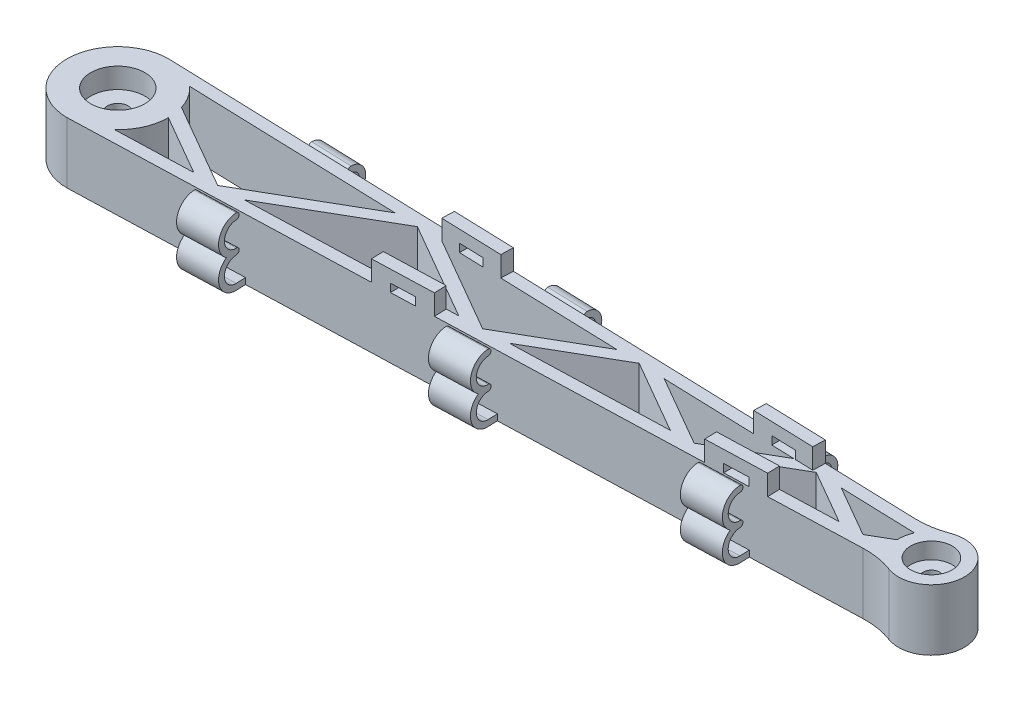
SolidWorks part; units mm, degrees
ref_plane "Front Plane" through (0, 0, 0) normal (0, 0, 1) x (1, 0, 0)
ref_plane "Top Plane" through (0, 0, 0) normal (0, 1, 0) x (1, 0, 0)
ref_plane "Right Plane" through (0, 0, 0) normal (1, 0, 0) x (0, 0, -1)
sketch "Sketch1" plane through (0, 0, 0) normal (0, 1, 0) x (1, 0, 0)
  line L0 (200, -6) -> (200, 6)
  line L1 (200, 6) -> (0, 12.5)
  line L2 (200, -6) -> (0, -12.5)
  line L3 (8.4358, 9.2243) -> (60.6202, 7.5283)
  line L4 (8.4358, -9.2243) -> (27.3057, -8.611)
  line L5 (197, 3.0959) -> (197, 2.5702)
  line L6 (32.986, -8.4264) -> (60.6202, 7.5283)
  line L7 (0, 0) -> (47.5809, 0) construction
  line L8 (39.3439, -8.2197) -> (66.3005, 7.3437)
  line L9 (32.986, -8.4264) -> (11.9305, 3.73)
  line L10 (66.3005, 7.3437) -> (90.3839, -6.5609)
  line L11 (72.6584, 7.137) -> (96.0642, -6.3763)
  line L12 (27.3057, -8.611) -> (12.4998, -0.0628)
  line L13 (96.0642, -6.3763) -> (116.9753, 5.6967)
  line L14 (102.4221, -6.1697) -> (122.6556, 5.5121)
  line L15 (122.6556, 5.5121) -> (140.7325, -4.9246)
  line L16 (129.0135, 5.3055) -> (146.4127, -4.74)
  line L17 (146.4127, -4.74) -> (161.9575, 4.2348)
  line L18 (152.7706, -4.5334) -> (167.6378, 4.0502)
  line L19 (167.6378, 4.0502) -> (180.9204, -3.6185)
  line L20 (173.9957, 3.8436) -> (186.6006, -3.4339)
  line L21 (186.6006, -3.4339) -> (197, 2.5702)
  line L22 (192.9585, -3.2273) -> (197, -0.8939)
  line L23 (197, -0.8939) -> (197, -3.0959)
  line L24 (173.9957, 3.8436) -> (197, 3.0959)
  line L25 (192.9585, -3.2273) -> (197, -3.0959)
  line L26 (180.6529, 0) -> (192.5483, 0) construction
  line L27 (160.6227, 0) -> (174.6529, 0) construction
  line L28 (152.7706, -4.5334) -> (180.9204, -3.6185)
  line L29 (129.0135, 5.3055) -> (161.9575, 4.2348)
  line L30 (138.2028, 0) -> (154.6227, 0) construction
  line L31 (113.1083, 0) -> (132.2028, 0) construction
  line L32 (102.4221, -6.1697) -> (140.7325, -4.9246)
  line L33 (85.02, 0) -> (107.1083, 0) construction
  line L34 (72.6584, 7.137) -> (116.9753, 5.6967)
  line L35 (53.5809, 0) -> (79.02, 0) construction
  line L36 (39.3439, -8.2197) -> (90.3839, -6.5609)
  circle A0 centre (0, 0) radius 6.65
  arc A1 (0, 12.5) -> (0, -12.5) centre (0, 0) ccw
  arc A2 (8.4358, -9.2243) -> (12.5, 0) centre (0, 0) ccw
  arc A3 (11.9305, 3.73) -> (8.4358, 9.2243) centre (0, 0) ccw
  point P6 (200, 0)
  dimension "D1" = 13.3
  dimension "D4" = 25
  dimension "D2" = 12
  dimension "D3" = 200
  dimension "D5" = 3
  dimension "D6" = 3
  dimension "D7" = 3
  dimension "D8" = 150
  dimension "D9" = 150
  dimension "D10" = 3
  dimension "D11" = 3
  dimension "D12" = 3
  dimension "D13" = 3
  dimension "D14" = 3
  dimension "D15" = 3
  dimension "D16" = 3
  dimension "D17" = 3
extrude "Boss-Extrude1" add sketch "Sketch1" along normal blind 15 contours L1 A1 L2 L0 L11 L34 L13 L16 L29 L17 L20 L24 L5 L21 L25 L22 L23 L28 L18 L19 L32 L14 L15 L36 L8 L10 A0 L4 A2 L12 L9 A3 L3 L6 region at (99.9305, 0, 7.1115)
ref_plane "Plane1" through (0, 10, 0) normal (0, 1, 0) x (1, 0, 0)
sketch "Sketch2" plane through (0, 10, 0) normal (0, 1, 0) x (1, 0, 0)
  circle A0 centre (0, 0) radius 6.65
  circle A1 centre (0, 0) radius 2.5
  dimension "D1" = 5
extrude "Boss-Extrude2" add sketch "Sketch2" against normal blind 5
sketch "Sketch3" plane through (0, 15, 0) normal (0, 1, 0) x (1, 0, 0)
  line L1 (200, -6) -> (200, 6) construction
  circle A1 centre (200, 0) radius 5.1
  circle A2 centre (200, 0) radius 8.1
  dimension "D1" = 10.2
  dimension "D2" = 3
extrude "Boss-Extrude3" add sketch "Sketch3" against normal through all
sketch "Sketch4" plane through (0, 15, 0) normal (0, 1, 0) x (1, 0, 0)
  line L0 (200, -5.1) -> (200, 5.1) construction
  circle A0 centre (200, 0) radius 5.1
extrude "Cut-Extrude1" cut sketch "Sketch4" against normal through all
fillet "Fillet1" radius 20 2 edges at (194.7527, 7.5, -6.1705) (194.7527, 7.5, 6.1705)
sketch "Sketch5" plane through (0, 10, 0) normal (0, 1, 0) x (1, 0, 0)
  circle A0 centre (200, 0) radius 5.1
  circle A1 centre (200, 0) radius 2
  dimension "D1" = 4
extrude "Boss-Extrude4" add sketch "Sketch5" against normal blind 6 and the other way blind 1
sketch "Sketch6" plane through (0, 15, 0) normal (0, 1, 0) x (1, 0, 0)
  line L7 (151.8463, 7.565) -> (166.8384, 7.0778)
  line L8 (151.8463, 7.565) -> (151.7489, 4.5666)
  line L9 (166.8384, 7.0778) -> (166.741, 4.0793)
  line L10 (151.7489, 4.5666) -> (166.741, 4.0793)
  line L11 (189.5339, 6.3401) -> (0, 12.5) construction
  line L12 (72.598, 10.1406) -> (87.5901, 9.6533)
  line L13 (72.598, 10.1406) -> (72.5006, 7.1421)
  line L14 (87.5901, 9.6533) -> (87.4927, 6.6549)
  line L15 (72.5006, 7.1421) -> (87.4927, 6.6549)
  line L16 (129.0135, 5.3055) -> (161.9575, 4.2348) construction
  line L17 (72.6584, 7.137) -> (116.9753, 5.6967) construction
  line L18 (166.8384, -7.0778) -> (151.8463, -7.565)
  line L19 (166.8384, -7.0778) -> (166.741, -4.0793)
  line L20 (151.8463, -7.565) -> (151.7489, -4.5666)
  line L21 (166.741, -4.0793) -> (151.7489, -4.5666)
  line L22 (189.5339, -6.3401) -> (0, -12.5) construction
  line L23 (152.7706, -4.5334) -> (180.9204, -3.6185) construction
  line L24 (87.4927, -9.6565) -> (72.5006, -10.1437)
  line L25 (87.4927, -9.6565) -> (87.3952, -6.6581)
  line L26 (72.5006, -10.1437) -> (72.4031, -7.1453)
  line L27 (87.3952, -6.6581) -> (72.4031, -7.1453)
  line L28 (39.3439, -8.2197) -> (90.3839, -6.5609) construction
  dimension "D1" = 15
  dimension "D2" = 15
extrude "Boss-Extrude5" add sketch "Sketch6" along normal blind 5
sketch "Sketch8" plane through (0, 0, 0) normal (0, 0, 1) x (1, 0, 0)
  line L0 (77.0006, 15) -> (83.0006, 15)
  line L1 (77.0006, 15) -> (77.0006, 17)
  line L2 (83.0006, 15) -> (83.0006, 17)
  line L3 (77.0006, 17) -> (83.0006, 17)
  line L4 (156.3463, 15) -> (162.3463, 15)
  line L5 (156.3463, 15) -> (156.3463, 17)
  line L6 (162.3463, 15) -> (162.3463, 17)
  line L7 (156.3463, 17) -> (162.3463, 17)
  line L8 (72.5006, 20) -> (72.5006, 15) construction
  line L9 (151.8463, 20) -> (151.8463, 15) construction
  line L10 (151.8463, 15) -> (87.4927, 15) construction
  dimension "D1" = 6
  dimension "D2" = 2
  dimension "D3" = 4.5
  dimension "D4" = 4.5
  dimension "D5" = 6
  dimension "D6" = 2
  dimension "D7" = 0
extrude "Cut-Extrude3" cut sketch "Sketch8" against normal blind 12 and the other way blind 12
ref_plane "Plane2" through (32.2133, 0, 1.0469) normal (-0.9995, 0, -0.0325) x (-0.0325, 0, 0.9995)
sketch "Sketch9" plane through (32.2133, 0, 1.0469) normal (-0.9995, 0, -0.0325) x (-0.0325, 0, 0.9995)
  line L0 (-12.4934, 15) -> (-12.4934, 0) construction
  line L1 (-12.4934, 0) -> (12.5, 0) construction
  line L3 (-15.9934, 0) -> (-12.4934, 0)
  line L5 (-15.9934, 1.5) -> (-12.4934, 1.5)
  line L6 (-12.4934, 0) -> (-12.4934, 1.5)
  arc A0 (-15.9934, 5.5) -> (-15.9934, 1.5) centre (-15.9934, 3.5) ccw
  arc A1 (-18.1585, 6.25) -> (-15.9934, 0) centre (-15.9934, 3.5) ccw
  arc A2 (-15.9934, 12.5) -> (-18.1585, 6.25) centre (-15.9934, 9) ccw
  arc A3 (-15.9934, 11) -> (-15.9934, 7) centre (-15.9934, 9) ccw
  arc A4 (-15.9934, 11) -> (-15.9934, 12.5) centre (-15.9934, 11.75) ccw
  arc A5 (-15.9934, 5.5) -> (-15.9934, 7) centre (-15.9934, 6.25) ccw
  dimension "D1" = 4
  dimension "D2" = 1.5
extrude "Boss-Extrude6" add sketch "Sketch9" against normal blind 10 contours A0 A5 A3 A4 A2 A1 L3 L6 L5 region at (32.7698, 5.4682, -16.0742)
ref_plane "Plane3" through (92.1817, 0, 2.9959) normal (0.9995, 0, 0.0325) x (0.0325, 0, -0.9995)
sketch "Sketch10" plane through (92.1817, 0, 2.9959) normal (0.9995, 0, 0.0325) x (0.0325, 0, -0.9995)
  line L3 (15.9934, 1.5) -> (12.4934, 1.5)
  line L4 (12.4934, 1.5) -> (12.4934, 0)
  line L5 (12.4934, 0) -> (15.9934, 0)
  line L6 (15.9934, 1.5) -> (12.4934, 1.5)
  line L7 (12.4934, 1.5) -> (12.4934, 0)
  line L8 (12.4934, 0) -> (15.9934, 0)
  arc A6 (15.9934, 1.5) -> (15.9934, 5.5) centre (15.9934, 3.5) ccw
  arc A7 (15.9934, 0) -> (18.1585, 6.25) centre (15.9934, 3.5) ccw
  arc A8 (18.1585, 6.25) -> (15.9934, 12.5) centre (15.9934, 9) ccw
  arc A9 (15.9934, 12.5) -> (15.9934, 11) centre (15.9934, 11.75) ccw
  arc A10 (15.9934, 7) -> (15.9934, 11) centre (15.9934, 9) ccw
  arc A11 (15.9934, 7) -> (15.9934, 5.5) centre (15.9934, 6.25) ccw
  arc A12 (15.9934, 1.5) -> (15.9934, 5.5) centre (15.9934, 3.5) ccw
  arc A13 (15.9934, 0) -> (18.1585, 6.25) centre (15.9934, 3.5) ccw
  arc A14 (18.1585, 6.25) -> (15.9934, 12.5) centre (15.9934, 9) ccw
  arc A15 (15.9934, 12.5) -> (15.9934, 11) centre (15.9934, 11.75) ccw
  arc A16 (15.9934, 7) -> (15.9934, 11) centre (15.9934, 9) ccw
  arc A17 (15.9934, 7) -> (15.9934, 5.5) centre (15.9934, 6.25) ccw
  dimension "D1" = 0
extrude "Boss-Extrude7" add sketch "Sketch10" along normal blind 10
ref_plane "Plane4" through (152.15, 0, 4.9449) normal (0.9995, 0, 0.0325) x (0.0325, 0, -0.9995)
sketch "Sketch11" plane through (152.15, 0, 4.9449) normal (0.9995, 0, 0.0325) x (0.0325, 0, -0.9995)
  line L3 (15.9934, 1.5) -> (12.4934, 1.5)
  line L4 (12.4934, 1.5) -> (12.4934, 0)
  line L5 (12.4934, 0) -> (15.9934, 0)
  line L6 (15.9934, 1.5) -> (12.4934, 1.5)
  line L7 (12.4934, 1.5) -> (12.4934, 0)
  line L8 (12.4934, 0) -> (15.9934, 0)
  arc A6 (15.9934, 1.5) -> (15.9934, 5.5) centre (15.9934, 3.5) ccw
  arc A7 (15.9934, 0) -> (18.1585, 6.25) centre (15.9934, 3.5) ccw
  arc A8 (18.1585, 6.25) -> (15.9934, 12.5) centre (15.9934, 9) ccw
  arc A9 (15.9934, 12.5) -> (15.9934, 11) centre (15.9934, 11.75) ccw
  arc A10 (15.9934, 7) -> (15.9934, 11) centre (15.9934, 9) ccw
  arc A11 (15.9934, 7) -> (15.9934, 5.5) centre (15.9934, 6.25) ccw
  arc A12 (15.9934, 1.5) -> (15.9934, 5.5) centre (15.9934, 3.5) ccw
  arc A13 (15.9934, 0) -> (18.1585, 6.25) centre (15.9934, 3.5) ccw
  arc A14 (18.1585, 6.25) -> (15.9934, 12.5) centre (15.9934, 9) ccw
  arc A15 (15.9934, 12.5) -> (15.9934, 11) centre (15.9934, 11.75) ccw
  arc A16 (15.9934, 7) -> (15.9934, 11) centre (15.9934, 9) ccw
  arc A17 (15.9934, 7) -> (15.9934, 5.5) centre (15.9934, 6.25) ccw
  dimension "D1" = 0
extrude "Boss-Extrude8" add sketch "Sketch11" along normal blind 10
ref_plane "Plane5" through (32.1159, 0, -1.0438) normal (-0.9995, 0, 0.0325) x (0.0325, 0, 0.9995)
sketch "Sketch12" plane through (32.1159, 0, -1.0438) normal (-0.9995, 0, 0.0325) x (0.0325, 0, 0.9995)
  line L0 (-0.0033, 0) -> (-0.0033, 15) construction
  line L1 (-12.5, 0) -> (12.4934, 0) construction
  line L2 (12.4934, 15) -> (-12.5, 15) construction
  line L9 (14.8582, 0) -> (10.3677, 0)
  line L10 (10.3677, 0) -> (10.3677, 1.5)
  line L11 (10.3677, 1.5) -> (14.8582, 1.5)
  ellipse E0 centre (14.8582, 8.25) end of major axis (14.8582, 9) minor radius 0.7484 (14.8582, 7.5) -> (14.8582, 9) cw
  ellipse E1 centre (14.8582, 12) end of major axis (14.8582, 15) minor radius 2.9937 (14.8582, 15) -> (14.8582, 9) cw
  ellipse E2 centre (14.8582, 15.75) end of major axis (14.8582, 16.5) minor radius 0.7484 (14.8582, 15) -> (14.8582, 16.5) cw
  ellipse E3 centre (14.8582, 12) end of major axis (14.8582, 16.5) minor radius 4.4905 (14.8582, 16.5) -> (17.3404, 8.25) cw
  ellipse E4 centre (14.8582, 4.5) end of major axis (14.8582, 9) minor radius 4.4905 (17.3404, 8.25) -> (14.8582, 0) cw
  ellipse E5 centre (14.8582, 4.5) end of major axis (14.8582, 7.5) minor radius 2.9937 (14.8582, 7.5) -> (14.8582, 1.5) cw
extrude "Boss-Extrude9" add sketch "Sketch12" against normal blind 10
ref_plane "Plane6" through (92.0842, 0, -2.9927) normal (0.9995, 0, -0.0325) x (-0.0325, 0, -0.9995)
sketch "Sketch13" plane through (92.0842, 0, -2.9927) normal (0.9995, 0, -0.0325) x (-0.0325, 0, -0.9995)
  line L3 (-14.8582, 0) -> (-12.4934, 0)
  line L4 (-12.4934, 0) -> (-12.4934, 1.5)
  line L5 (-12.4934, 1.5) -> (-14.8582, 1.5)
  line L6 (-14.8582, 0) -> (-12.4934, 0)
  line L7 (-12.4934, 0) -> (-12.4934, 1.5)
  line L8 (-12.4934, 1.5) -> (-14.8582, 1.5)
  ellipse E6 centre (-14.8582, 4.5) end of major axis (-14.8582, 7.5) minor radius 2.9937 (-14.8582, 7.5) -> (-14.8582, 1.5) ccw
  ellipse E7 centre (-14.8582, 8.25) end of major axis (-14.8582, 9) minor radius 0.7484 (-14.8582, 7.5) -> (-14.8582, 9) ccw
  ellipse E8 centre (-14.8582, 12) end of major axis (-14.8582, 15) minor radius 2.9937 (-14.8582, 15) -> (-14.8582, 9) ccw
  ellipse E9 centre (-14.8582, 15.75) end of major axis (-14.8582, 16.5) minor radius 0.7484 (-14.8582, 15) -> (-14.8582, 16.5) ccw
  ellipse E10 centre (-14.8582, 12) end of major axis (-14.8582, 16.5) minor radius 4.4905 (-14.8582, 16.5) -> (-17.3404, 8.25) ccw
  ellipse E11 centre (-14.8582, 4.5) end of major axis (-14.8582, 9) minor radius 4.4905 (-17.3404, 8.25) -> (-14.8582, 0) ccw
  ellipse E12 centre (-14.8582, 4.5) end of major axis (-14.8582, 7.5) minor radius 2.9937 (-14.8582, 7.5) -> (-14.8582, 1.5) ccw
  ellipse E13 centre (-14.8582, 8.25) end of major axis (-14.8582, 9) minor radius 0.7484 (-14.8582, 7.5) -> (-14.8582, 9) ccw
  ellipse E14 centre (-14.8582, 12) end of major axis (-14.8582, 15) minor radius 2.9937 (-14.8582, 15) -> (-14.8582, 9) ccw
  ellipse E15 centre (-14.8582, 15.75) end of major axis (-14.8582, 16.5) minor radius 0.7484 (-14.8582, 15) -> (-14.8582, 16.5) ccw
  ellipse E16 centre (-14.8582, 12) end of major axis (-14.8582, 16.5) minor radius 4.4905 (-14.8582, 16.5) -> (-17.3404, 8.25) ccw
  ellipse E17 centre (-14.8582, 4.5) end of major axis (-14.8582, 9) minor radius 4.4905 (-17.3404, 8.25) -> (-14.8582, 0) ccw
  dimension "D1" = 0
extrude "Boss-Extrude10" add sketch "Sketch13" along normal blind 10
ref_plane "Plane7" through (152.0525, 0, -4.9417) normal (0.9995, 0, -0.0325) x (-0.0325, 0, -0.9995)
sketch "Sketch14" plane through (152.0525, 0, -4.9417) normal (0.9995, 0, -0.0325) x (-0.0325, 0, -0.9995)
  line L3 (-14.8582, 0) -> (-12.4934, 0)
  line L4 (-12.4934, 0) -> (-12.4934, 1.5)
  line L5 (-12.4934, 1.5) -> (-14.8582, 1.5)
  line L6 (-14.8582, 0) -> (-12.4934, 0)
  line L7 (-12.4934, 0) -> (-12.4934, 1.5)
  line L8 (-12.4934, 1.5) -> (-14.8582, 1.5)
  ellipse E6 centre (-14.8582, 4.5) end of major axis (-14.8582, 9) minor radius 4.4905 (-17.3404, 8.25) -> (-14.8582, 0) ccw
  ellipse E7 centre (-14.8582, 4.5) end of major axis (-14.8582, 7.5) minor radius 2.9937 (-14.8582, 7.5) -> (-14.8582, 1.5) ccw
  ellipse E8 centre (-14.8582, 8.25) end of major axis (-14.8582, 9) minor radius 0.7484 (-14.8582, 7.5) -> (-14.8582, 9) ccw
  ellipse E9 centre (-14.8582, 12) end of major axis (-14.8582, 15) minor radius 2.9937 (-14.8582, 15) -> (-14.8582, 9) ccw
  ellipse E10 centre (-14.8582, 15.75) end of major axis (-14.8582, 16.5) minor radius 0.7484 (-14.8582, 15) -> (-14.8582, 16.5) ccw
  ellipse E11 centre (-14.8582, 12) end of major axis (-14.8582, 16.5) minor radius 4.4905 (-14.8582, 16.5) -> (-17.3404, 8.25) ccw
  ellipse E12 centre (-14.8582, 4.5) end of major axis (-14.8582, 9) minor radius 4.4905 (-17.3404, 8.25) -> (-14.8582, 0) ccw
  ellipse E13 centre (-14.8582, 4.5) end of major axis (-14.8582, 7.5) minor radius 2.9937 (-14.8582, 7.5) -> (-14.8582, 1.5) ccw
  ellipse E14 centre (-14.8582, 8.25) end of major axis (-14.8582, 9) minor radius 0.7484 (-14.8582, 7.5) -> (-14.8582, 9) ccw
  ellipse E15 centre (-14.8582, 12) end of major axis (-14.8582, 15) minor radius 2.9937 (-14.8582, 15) -> (-14.8582, 9) ccw
  ellipse E16 centre (-14.8582, 15.75) end of major axis (-14.8582, 16.5) minor radius 0.7484 (-14.8582, 15) -> (-14.8582, 16.5) ccw
  ellipse E17 centre (-14.8582, 12) end of major axis (-14.8582, 16.5) minor radius 4.4905 (-14.8582, 16.5) -> (-17.3404, 8.25) ccw
  dimension "D1" = 0
extrude "Boss-Extrude11" add sketch "Sketch14" along normal blind 10
